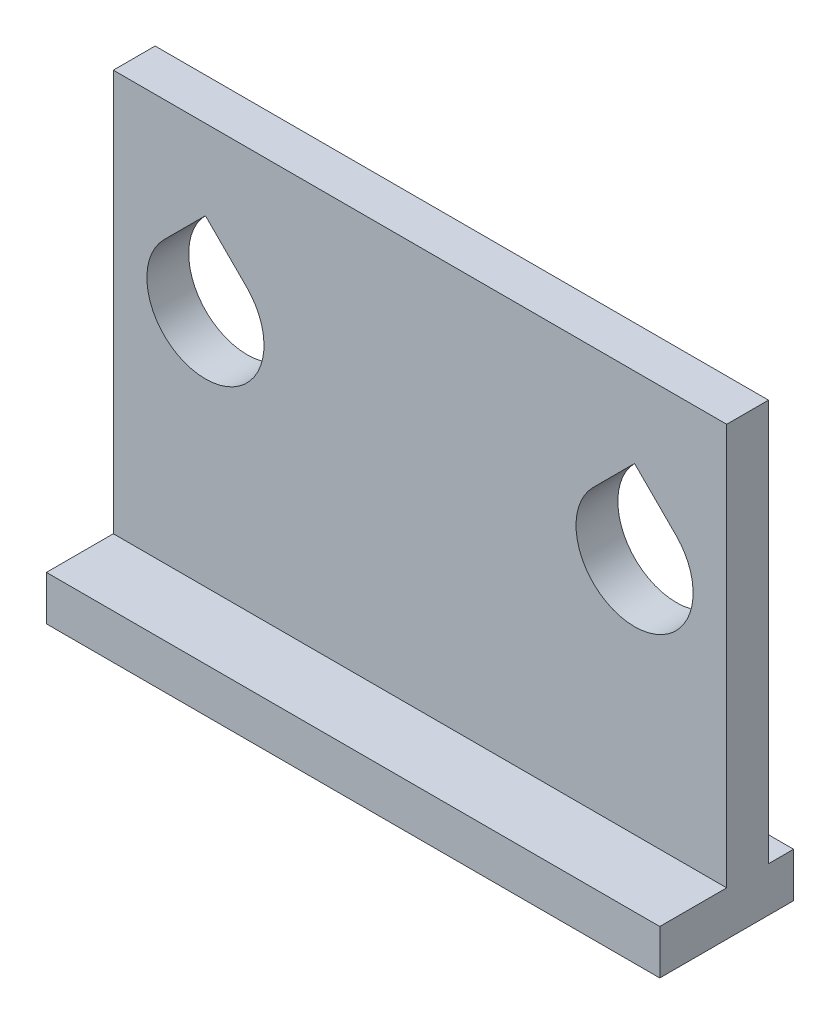
SolidWorks part; units mm, degrees
ref_plane "Front Plane" through (0, 0, 0) normal (0, 0, 1) x (1, 0, 0)
ref_plane "Top Plane" through (0, 0, 0) normal (0, 1, 0) x (1, 0, 0)
ref_plane "Right Plane" through (0, 0, 0) normal (1, 0, 0) x (0, 0, -1)
sketch "Sketch1" plane through (0, 0, 0) normal (0, 0, 1) x (1, 0, 0)
  line L0 (-38.481, 50.8) -> (38.481, 50.8) construction
  line L1 (-55, 0) -> (55, 0)
  line L2 (-55, 0) -> (-55, 80)
  line L3 (-55, 80) -> (55, 80)
  line L4 (55, 0) -> (55, 80)
  line L5 (38.481, 50.8) -> (0, 50.8)
  line L6 (0, 50.8) -> (0, 0) construction
  line L7 (-45.9056, 58.2246) -> (-38.481, 65.6492)
  line L8 (-38.481, 65.6492) -> (-31.0564, 58.2246)
  line L9 (31.0564, 58.2246) -> (38.481, 65.6492)
  line L10 (38.481, 65.6492) -> (45.9056, 58.2246)
  circle A0 centre (-38.481, 50.8) radius 10.5
  circle A1 centre (38.481, 50.8) radius 10.5
  point P4 (0, 0)
  dimension "D4" = 21
  dimension "D5" = 21
  dimension "D1" = 80
  dimension "D2" = 110
  dimension "D3" = 76.962
  dimension "D6" = 50.8
  dimension "D7" = 45
  dimension "D8" = 90
  dimension "D9" = 45
  dimension "D10" = 90
extrude "Boss-Extrude1" add sketch "Sketch1" along normal blind 7.5 contours L1 L4 L3 L2 A1 A0 region at (0, 38.9407, 0)
sketch "Sketch3" plane through (0, 0, 7.5) normal (0, 0, 1) x (1, 0, 0)
  line L0 (55, 0) -> (55, 80) construction
  line L1 (-55, 0) -> (55, 0)
  line L2 (-55, 0) -> (-55, 8)
  line L3 (-55, 8) -> (55, 8)
  line L4 (55, 0) -> (55, 8)
extrude "Boss-Extrude2" add sketch "Sketch3" along normal blind 12 and the other way blind 12
equation "\"shaftDiam\" = 20mm"
equation "\"keyW\" = 8mm"
equation "\"keyL\" = 10mm"
equation "\"clearance\" = 1mm"
equation "\"handleShaftLen\" = 60mm"
equation "\"panelH\" = 80mm"
equation "\"panelW\" = 110mm"
equation "\"D1@Sketch1\"=\"panelH\""
equation "\"D2@Sketch1\"=\"panelW\""
equation "\"D3@Sketch1\"=3.03in"
equation "\"D4@Sketch1\" = \"shaftDiam\" + \"clearance\""
equation "\"D5@Sketch1\" = \"shaftDiam\" + \"clearance\""
equation "\"D6@Sketch1\"=4in/2"
equation "\"D1@Boss-Extrude1\"=\"handleShaftLen\"/8"
equation "\"D1@Sketch3\"=\"panelH\"/10"
equation "\"D1@Boss-Extrude2\"=\"handleShaftLen\"/5"
equation "\"D2@Boss-Extrude2\"=\"handleShaftLen\"/5"
